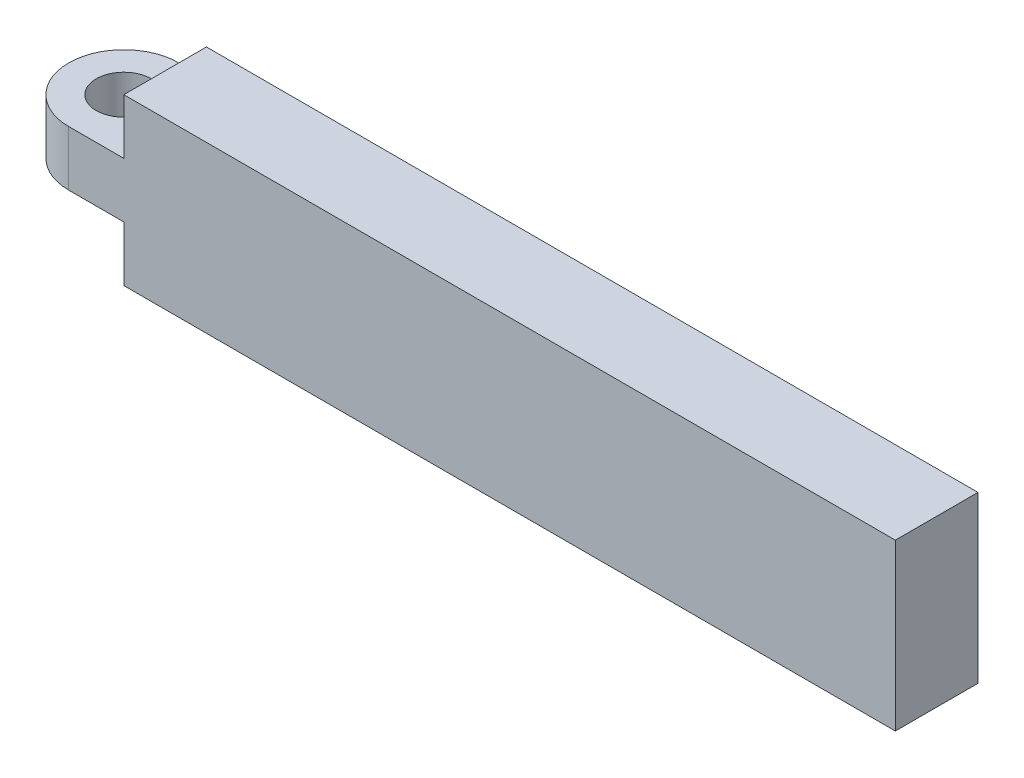
SolidWorks part; units mm, degrees
ref_plane "Front Plane" through (0, 0, 0) normal (0, 0, 1) x (1, 0, 0)
ref_plane "Top Plane" through (0, 0, 0) normal (0, 1, 0) x (1, 0, 0)
ref_plane "Right Plane" through (0, 0, 0) normal (1, 0, 0) x (0, 0, -1)
sketch "Sketch1" plane through (0, 0, 0) normal (0, 1, 0) x (1, 0, 0)
  line L1 (-7, 1) -> (7, 1)
  line L2 (-7, 1) -> (-7, -1)
  line L3 (-7, -1) -> (7, -1)
  line L4 (7, 1) -> (7, -1)
  line L5 (-7, 1) -> (7, -1) construction
  line L6 (-7, -1) -> (7, 1) construction
  point P0 (0, 0)
  dimension "D1" = 14
  dimension "D2" = 2
extrude "Boss-Extrude1" add sketch "Sketch1" along normal blind 3
chamfer "Chamfer1" distance 0.5 angle 45 3 edges at (0, 0, -1) (7, 1.5, -1) (0, 3, -1)
sketch "Sketch2" plane through (-7, 0, 0) normal (-1, 0, 0) x (0, 0, 1)
  line L0 (1, 3) -> (1, 0) construction
  line L1 (-1, 1) -> (1, 1)
  line L2 (-1, 1) -> (-1, 2)
  line L3 (-1, 2) -> (1, 2)
  line L4 (1, 1) -> (1, 2)
  line L5 (-1, 1) -> (1, 2) construction
  line L6 (-1, 2) -> (1, 1) construction
  point P0 (0, 1.5)
  point P8 (1, 1.5)
  dimension "D1" = 1
extrude "Boss-Extrude2" add sketch "Sketch2" along normal blind 2
sketch "Sketch3" plane through (0, 2, 0) normal (0, 1, 0) x (1, 0, 0)
  line L0 (-9, -1) -> (-7, -1) construction
  line L1 (-9, -1) -> (-9, 1) construction
  line L6 (-7, -1) -> (-7, 1)
  line L7 (-7, 1) -> (-9, 1)
  line L8 (-9, 1) -> (-9, -1)
  line L9 (-9, -1) -> (-7, -1)
  line L10 (-7, -1) -> (-7, 1)
  line L11 (-7, 1) -> (-9, 1)
  line L12 (-9, 1) -> (-9, -1)
  line L13 (-9, -1) -> (-7, -1)
  circle A0 centre (-8, 0) radius 1
  circle A1 centre (-8, 0) radius 0.5
  point P4 (-8, -1)
  point P7 (-9, 0)
  line M7 (-9, 1) -> (-9, -1)
  line M8 (-9, -1) -> (-7, -1)
  dimension "D1" = 2
  dimension "D2" = 0.5
  dimension "D3" = 0
extrude "Cut-Extrude1" cut sketch "Sketch3" against normal blind 2 contours A1 | A0 L11 M7 | A0 L12 M8 region at (-8.7766, 2, 0.7766) region at (-8.7766, 2, -0.7766) region at (-8, 2, 0)
